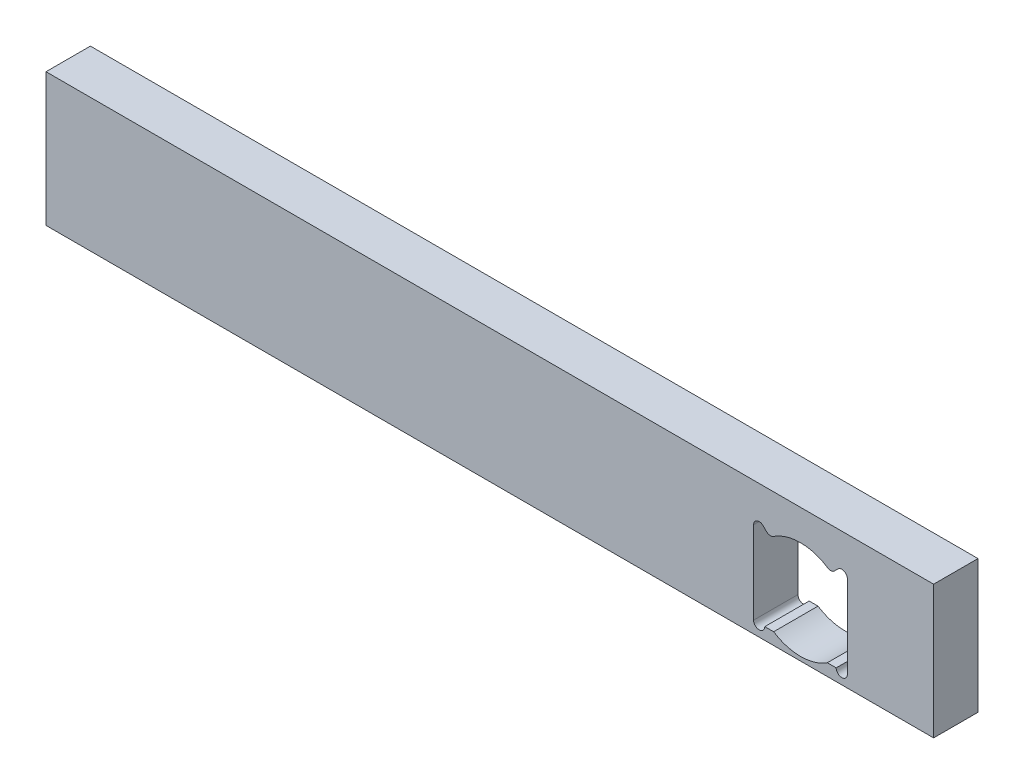
SolidWorks part; units mm, degrees
material "6061-T6 (SS)"
ref_plane "Front Plane" through (0, 0, 0) normal (0, 0, 1) x (1, 0, 0)
ref_plane "Top Plane" through (0, 0, 0) normal (0, 1, 0) x (1, 0, 0)
ref_plane "Right Plane" through (0, 0, 0) normal (1, 0, 0) x (0, 0, -1)
sketch "Sketch1" plane through (0, 0, 0) normal (0, 0, 1) x (1, 0, 0)
  line L1 (-215.9, -19.05) -> (38.1, -19.05)
  line L2 (-215.9, -19.05) -> (-215.9, 19.05)
  line L3 (-215.9, 19.05) -> (38.1, 19.05)
  line L4 (38.1, -19.05) -> (38.1, 19.05)
  line L5 (-215.9, -19.05) -> (38.1, 19.05) construction
  line L6 (-215.9, 19.05) -> (38.1, -19.05) construction
  line L7 (-215.9, 19.05) -> (38.1, 19.05)
  line L8 (-215.9, 19.05) -> (-215.9, -19.05)
  line L11 (-215.9, -19.05) -> (38.1, -19.05)
  line L12 (-215.9, -19.05) -> (-215.9, 19.05)
  line L15 (38.1, -19.05) -> (-215.9, -19.05)
  line L16 (38.1, -19.05) -> (38.1, 19.05)
  line L20 (38.1, -19.05) -> (38.1, 19.05)
  point P0 (0, 0)
  point P6 (34.2781, -19.9218)
  point P7 (29.0921, 19.9218)
  point P9 (0, 0)
  point P10 (0, 0)
  point P11 (29.3451, 18.2775)
  point P12 (28.5354, 18.8025)
  point P14 (-88.9, 0)
  dimension "D1" = 38.1
  dimension "D2" = 254
  dimension "D3" = 38.1
extrude "Boss-Extrude1" add sketch "Sketch1" along normal blind 12.7 contours L4 L3 L2 L1 region at (-88.9, 0, 0)
sketch "Sketch5" plane through (0, 0, 12.7) normal (0, 0, 1) x (1, 0, 0)
  line L0 (0, -3.81) -> (11.8187, 8.0087) construction
  line L1 (0, -3.81) -> (11.8187, -3.81) construction
  line L2 (0, -3.81) -> (0, 8.0087) construction
  line L3 (0, 8.0087) -> (11.8187, 8.0087) construction
  line L4 (11.8187, -3.81) -> (11.8187, 8.0087) construction
  line L5 (-10.6872, 9.1402) -> (-8.7721, 7.2252)
  line L6 (0, -3.81) -> (11.8187, -3.81) construction
  line L7 (0, -3.81) -> (0, -15.6287) construction
  line L8 (0, -15.6287) -> (11.8187, -15.6287) construction
  line L9 (11.8187, -3.81) -> (11.8187, -15.6287) construction
  line L10 (0, -3.81) -> (-11.8187, -3.81) construction
  line L11 (0, -3.81) -> (0, -15.6287) construction
  line L12 (0, -15.6287) -> (-11.8187, -15.6287) construction
  line L13 (-11.8187, -3.81) -> (-11.8187, -15.6287) construction
  line L14 (0, -3.81) -> (-11.8187, -3.81) construction
  line L15 (0, -3.81) -> (0, 8.0087) construction
  line L16 (0, 8.0087) -> (-11.8187, 8.0087) construction
  line L17 (-11.8187, -3.81) -> (-11.8187, 8.0087) construction
  line L18 (-13.4189, 8.0087) -> (-13.4189, -15.6287)
  line L19 (13.4189, 8.0087) -> (13.4189, -15.6287)
  line L20 (10.9269, 9.3374) -> (8.7958, 7.2063)
  line L21 (-13.4189, -15.6287) -> (-13.4189, -19.05)
  line L22 (-215.9, -19.05) -> (38.1, -19.05) construction
  line L23 (-13.4189, -19.05) -> (13.4189, -19.05)
  line L24 (13.4189, -19.05) -> (13.4189, -15.6287)
  line L25 (-10.2185, -15.6287) -> (-7.6839, -15.6287)
  line L26 (10.2185, -15.6287) -> (7.6839, -15.6287)
  circle A0 centre (0, -3.81) radius 14.097 construction
  circle A1 centre (11.8187, 8.0087) radius 1.6002
  circle A2 centre (-11.8187, 8.0087) radius 1.6002
  circle A3 centre (-11.8187, -15.6287) radius 1.6002
  circle A4 centre (11.8187, -15.6287) radius 1.6002
  arc A5 (-8.7721, 7.2252) -> (8.7958, 7.2063) centre (0, -3.81) cw
  arc A6 (-7.6839, -15.6287) -> (7.6839, -15.6287) centre (0, -3.81) ccw
  point P6 (9.9681, 6.1581)
  point P7 (10.6872, 6.8772)
  line M8 (-215.9, -19.05) -> (38.1, -19.05)
  dimension "D1" = 28.194
  dimension "D2" = 3.2004
  dimension "D3" = 1.017
  dimension "D4" = 45
  dimension "D5" = 45
  dimension "D6" = 15.24
extrude "Cut-Extrude4" cut sketch "Sketch5" against normal through all contours A5 L5 A2 L18 A3 L21 L24 A4 L19 A1 L20 M8 | A4 | A3 | A2 | A1 L20 region at (-0.0011, -3.8263, 12.7) region at (-11.8187, 8.0087, 12.7) region at (-11.8187, -15.6287, 12.7) region at (11.8205, 8.007, 12.7) region at (11.8187, -15.6287, 12.7)
fillet "Fillet1" radius 1.5875 2 edges at (8.7958, 7.2063, 6.35) (-8.7721, 7.2252, 6.35)
